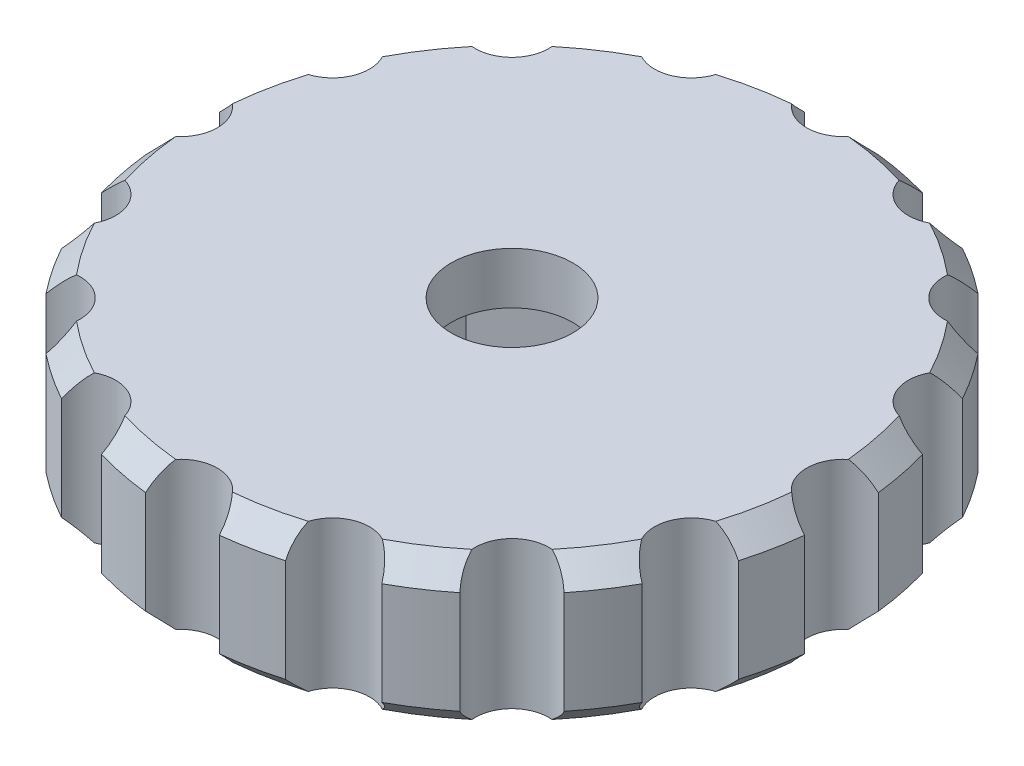
SolidWorks part; units mm, degrees
ref_plane "Front Plane" through (0, 0, 0) normal (0, 0, 1) x (1, 0, 0)
ref_plane "Top Plane" through (0, 0, 0) normal (0, 1, 0) x (1, 0, 0)
ref_plane "Right Plane" through (0, 0, 0) normal (1, 0, 0) x (0, 0, -1)
sketch "Sketch1" plane through (0, 0, 0) normal (0, 1, 0) x (1, 0, 0)
  circle A0 centre (0, 0) radius 9
  dimension "D1" = 18
extrude "Boss-Extrude1" add sketch "Sketch1" along normal blind 4
sketch "Sketch2" plane through (0, 0, 0) normal (0, -1, 0) x (1, 0, 0)
  line L1 (2.95, 1.7032) -> (0, 3.4064)
  line L2 (0, 3.4064) -> (-2.95, 1.7032)
  line L3 (-2.95, 1.7032) -> (-2.95, -1.7032)
  line L4 (-2.95, -1.7032) -> (0, -3.4064)
  line L5 (0, -3.4064) -> (2.95, -1.7032)
  line L6 (2.95, -1.7032) -> (2.95, 1.7032)
  circle A0 centre (0, 0) radius 2.95 construction
  dimension "D1" = 5.9
extrude "Cut-Extrude1" cut sketch "Sketch2" against normal blind 2.6
sketch "Sketch3" plane through (0, 0, 0) normal (0, -1, 0) x (1, 0, 0)
  circle A0 centre (0, 0) radius 1.65
  dimension "D1" = 3.3
extrude "Cut-Extrude2" cut sketch "Sketch3" against normal through all
sketch "Sketch4" plane through (0, 4, 0) normal (0, 1, 0) x (1, 0, 0)
  arc A0 (-1, 8.9443) -> (1, 8.9443) centre (0, 9) ccw
  circle A1 centre (0, 0) radius 9 construction
  arc A2 (2.4989, 8.6461) -> (4.3467, 7.8807) centre (3.4442, 8.3149) ccw
  arc A3 (5.6174, 7.0317) -> (7.0317, 5.6174) centre (6.364, 6.364) ccw
  arc A4 (7.8807, 4.3467) -> (8.6461, 2.4989) centre (8.3149, 3.4442) ccw
  arc A5 (8.9443, 1) -> (8.9443, -1) centre (9, 0) ccw
  arc A6 (8.6461, -2.4989) -> (7.8807, -4.3467) centre (8.3149, -3.4442) ccw
  arc A7 (7.0317, -5.6174) -> (5.6174, -7.0317) centre (6.364, -6.364) ccw
  arc A8 (4.3467, -7.8807) -> (2.4989, -8.6461) centre (3.4442, -8.3149) ccw
  arc A9 (1, -8.9443) -> (-1, -8.9443) centre (0, -9) ccw
  arc A10 (-2.4989, -8.6461) -> (-4.3467, -7.8807) centre (-3.4442, -8.3149) ccw
  arc A11 (-5.6174, -7.0317) -> (-7.0317, -5.6174) centre (-6.364, -6.364) ccw
  arc A12 (-7.8807, -4.3467) -> (-8.6461, -2.4989) centre (-8.3149, -3.4442) ccw
  arc A13 (-8.9443, -1) -> (-8.9443, 1) centre (-9, 0) ccw
  arc A14 (-8.6461, 2.4989) -> (-7.8807, 4.3467) centre (-8.3149, 3.4442) ccw
  arc A15 (-7.0317, 5.6174) -> (-5.6174, 7.0317) centre (-6.364, 6.364) ccw
  arc A16 (-4.3467, 7.8807) -> (-2.4989, 8.6461) centre (-3.4442, 8.3149) ccw
  arc A17 (-2.4989, 8.6461) -> (-4.3467, 7.8807) centre (0, 0) ccw
  arc A18 (-5.6174, 7.0317) -> (-7.0317, 5.6174) centre (0, 0) ccw
  arc A19 (-7.8807, 4.3467) -> (-8.6461, 2.4989) centre (0, 0) ccw
  arc A20 (-8.9443, 1) -> (-8.9443, -1) centre (0, 0) ccw
  arc A21 (-8.6461, -2.4989) -> (-7.8807, -4.3467) centre (0, 0) ccw
  arc A22 (-7.0317, -5.6174) -> (-5.6174, -7.0317) centre (0, 0) ccw
  arc A23 (-4.3467, -7.8807) -> (-2.4989, -8.6461) centre (0, 0) ccw
  arc A24 (-1, -8.9443) -> (1, -8.9443) centre (0, 0) ccw
  arc A25 (2.4989, -8.6461) -> (4.3467, -7.8807) centre (0, 0) ccw
  arc A26 (5.6174, -7.0317) -> (7.0317, -5.6174) centre (0, 0) ccw
  arc A27 (7.8807, -4.3467) -> (8.6461, -2.4989) centre (0, 0) ccw
  arc A28 (8.9443, -1) -> (8.9443, 1) centre (0, 0) ccw
  arc A29 (8.6461, 2.4989) -> (7.8807, 4.3467) centre (0, 0) ccw
  arc A30 (7.0317, 5.6174) -> (5.6174, 7.0317) centre (0, 0) ccw
  arc A31 (4.3467, 7.8807) -> (2.4989, 8.6461) centre (0, 0) ccw
  arc A32 (1, 8.9443) -> (-1, 8.9443) centre (0, 0) ccw
  dimension "D1" = 2
  dimension "D2" = 16
extrude "Cut-Extrude4" cut sketch "Sketch4" against normal through all
sketch "Sketch5" plane through (0, 0, 0) normal (0, 0, 1) x (1, 0, 0)
  line L0 (0, 0) -> (0, 4) construction
  line L1 (8.2943, 4.1) -> (9.0443, 3.35)
  line L2 (9.0443, 3.35) -> (9.0443, 4.1)
  line L3 (9.0443, 4.1) -> (8.2943, 4.1)
  line L4 (1, 4) -> (-1, 4) construction
  line L5 (8.9443, 0) -> (8.9443, 4) construction
  line L6 (0, 2) -> (8.9095, 2) construction
  line L7 (9.0443, -0.1) -> (8.2943, -0.1)
  line L8 (9.0443, 0.65) -> (9.0443, -0.1)
  line L9 (8.2943, -0.1) -> (9.0443, 0.65)
  dimension "D1" = 0.1
  dimension "D2" = 0.1
  dimension "D4" = 0.75
revolve "Cut-Revolve1" cut sketch "Sketch5" angle 360 about L0
